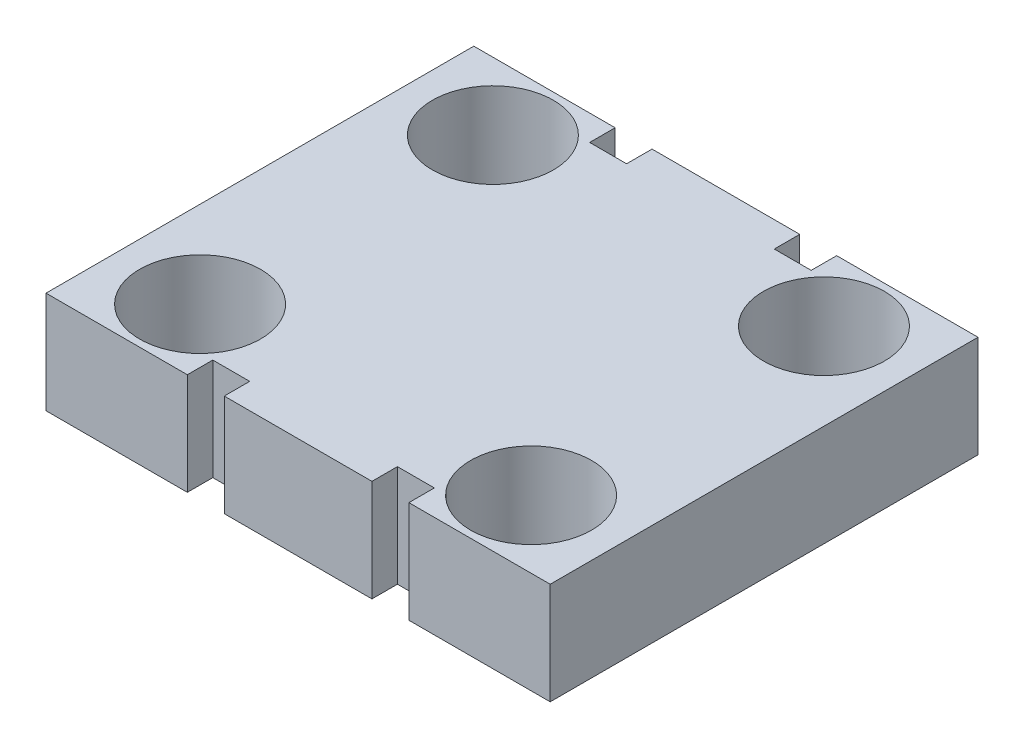
SolidWorks part; units mm, degrees
ref_plane "Płaszczyzna przednia" through (0, 0, 0) normal (0, 0, 1) x (1, 0, 0)
ref_plane "Płaszczyzna górna" through (0, 0, 0) normal (0, 1, 0) x (1, 0, 0)
ref_plane "Płaszczyzna prawa" through (0, 0, 0) normal (1, 0, 0) x (0, 0, -1)
sketch "Sketch1" plane through (0, 0, 0) normal (0, 1, 0) x (1, 0, 0)
  line L1 (-40, 34) -> (0, 34)
  line L2 (-40, 34) -> (-40, 0)
  line L3 (-40, 0) -> (0, 0)
  line L4 (0, 34) -> (0, 0)
  dimension "D1" = 40
  dimension "D2" = 34
extrude "Boss-Extrude1" add sketch "Sketch1" along normal blind 8
sketch "Sketch2" plane through (0, 8, 0) normal (0, 1, 0) x (1, 0, 0)
  line L0 (-40, 17) -> (-9.7076, 17) construction
  line L1 (-20, 34) -> (-20, -8.7627) construction
  line L2 (-40, 34) -> (-40, 0) construction
  line L3 (0, 34) -> (-40, 34) construction
  circle A0 centre (-33, 28.5) radius 4.75
  circle A1 centre (-33, 5.5) radius 4.75
  circle A2 centre (-7, 5.5) radius 4.75
  circle A3 centre (-7, 28.5) radius 4.75
  dimension "D1" = 9.5
  dimension "D2" = 7
  dimension "D3" = 5.5
extrude "Cut-Extrude1" cut sketch "Sketch2" against normal blind 7
sketch "Sketch3" plane through (0, 0, 0) normal (0, -1, 0) x (1, 0, 0)
  line L0 (-40, 0) -> (0, -34) construction
  circle A0 centre (-20, -17) radius 5.5
  point P3 (-20, -17)
  dimension "D1" = 11
extrude "Cut-Extrude2" cut sketch "Sketch3" against normal blind 6
sketch "Sketch4" plane through (0, 0, 0) normal (0, -1, 0) x (1, 0, 0)
  line L0 (-20, 0) -> (-20, -34) construction
  line L1 (-40, -17) -> (0, -17) construction
  line L2 (-40, 0) -> (0, 0) construction
  line L3 (0, -34) -> (-40, -34) construction
  line L4 (-40, -34) -> (-40, 0) construction
  line L5 (0, 0) -> (0, -34) construction
  line L6 (-11.5, -2) -> (-14, -2)
  line L7 (-28.5, 0) -> (-26, 0)
  line L8 (-28.5, 0) -> (-28.5, -2)
  line L9 (-28.5, -2) -> (-26, -2)
  line L10 (-26, 0) -> (-26, -2)
  line L11 (-14, 0) -> (-14, -2)
  line L12 (-11.5, 0) -> (-14, 0)
  line L13 (-11.5, 0) -> (-11.5, -2)
  line L14 (-11.5, -34) -> (-11.5, -32)
  line L15 (-11.5, -34) -> (-14, -34)
  line L16 (-14, -34) -> (-14, -32)
  line L17 (-11.5, -32) -> (-14, -32)
  line L18 (-28.5, -32) -> (-26, -32)
  line L19 (-26, -34) -> (-26, -32)
  line L20 (-28.5, -34) -> (-26, -34)
  line L21 (-28.5, -34) -> (-28.5, -32)
  dimension "D1" = 2.5
  dimension "D2" = 2
  dimension "D3" = 6
extrude "Cut-Extrude3" cut sketch "Sketch4" against normal blind 15
sketch "Sketch5" plane through (0, 0, 0) normal (0, -1, 0) x (1, 0, 0)
  line L40 (-39.8, -33.8) -> (-28.7, -33.8)
  line L41 (-28.7, -33.8) -> (-28.7, -31.8)
  line L42 (-28.7, -31.8) -> (-25.8, -31.8)
  line L43 (-25.8, -31.8) -> (-25.8, -33.8)
  line L44 (-25.8, -33.8) -> (-14.2, -33.8)
  line L45 (-14.2, -33.8) -> (-14.2, -31.8)
  line L46 (-14.2, -31.8) -> (-11.3, -31.8)
  line L47 (-11.3, -31.8) -> (-11.3, -33.8)
  line L48 (-11.3, -33.8) -> (-0.2, -33.8)
  line L49 (-0.2, -33.8) -> (-0.2, -0.2)
  line L50 (-0.2, -0.2) -> (-11.3, -0.2)
  line L51 (-11.3, -0.2) -> (-11.3, -2.2)
  line L52 (-11.3, -2.2) -> (-14.2, -2.2)
  line L53 (-14.2, -2.2) -> (-14.2, -0.2)
  line L54 (-14.2, -0.2) -> (-25.8, -0.2)
  line L55 (-25.8, -0.2) -> (-25.8, -2.2)
  line L56 (-25.8, -2.2) -> (-28.7, -2.2)
  line L57 (-28.7, -2.2) -> (-28.7, -0.2)
  line L58 (-28.7, -0.2) -> (-39.8, -0.2)
  line L59 (-39.8, -0.2) -> (-39.8, -33.8)
  line L60 (-39.8, -33.8) -> (-28.7, -33.8)
  line L61 (-28.7, -33.8) -> (-28.7, -31.8)
  line L62 (-28.7, -31.8) -> (-25.8, -31.8)
  line L63 (-25.8, -31.8) -> (-25.8, -33.8)
  line L64 (-25.8, -33.8) -> (-14.2, -33.8)
  line L65 (-14.2, -33.8) -> (-14.2, -31.8)
  line L66 (-14.2, -31.8) -> (-11.3, -31.8)
  line L67 (-11.3, -31.8) -> (-11.3, -33.8)
  line L68 (-11.3, -33.8) -> (-0.2, -33.8)
  line L69 (-0.2, -33.8) -> (-0.2, -0.2)
  line L70 (-0.2, -0.2) -> (-11.3, -0.2)
  line L71 (-11.3, -0.2) -> (-11.3, -2.2)
  line L72 (-11.3, -2.2) -> (-14.2, -2.2)
  line L73 (-14.2, -2.2) -> (-14.2, -0.2)
  line L74 (-14.2, -0.2) -> (-25.8, -0.2)
  line L75 (-25.8, -0.2) -> (-25.8, -2.2)
  line L76 (-25.8, -2.2) -> (-28.7, -2.2)
  line L77 (-28.7, -2.2) -> (-28.7, -0.2)
  line L78 (-28.7, -0.2) -> (-39.8, -0.2)
  line L79 (-39.8, -0.2) -> (-39.8, -33.8)
  line L80 (-40, -34) -> (-28.5, -34)
  line L81 (-28.5, -34) -> (-28.5, -32)
  line L82 (-28.5, -32) -> (-26, -32)
  line L83 (-26, -32) -> (-26, -34)
  line L84 (-26, -34) -> (-14, -34)
  line L85 (-14, -34) -> (-14, -32)
  line L86 (-14, -32) -> (-11.5, -32)
  line L87 (-11.5, -32) -> (-11.5, -34)
  line L88 (-11.5, -34) -> (0, -34)
  line L89 (0, -34) -> (0, 0)
  line L90 (0, 0) -> (-11.5, 0)
  line L91 (-11.5, 0) -> (-11.5, -2)
  line L92 (-11.5, -2) -> (-14, -2)
  line L93 (-14, -2) -> (-14, 0)
  line L94 (-14, 0) -> (-26, 0)
  line L95 (-26, 0) -> (-26, -2)
  line L96 (-26, -2) -> (-28.5, -2)
  line L97 (-28.5, -2) -> (-28.5, 0)
  line L98 (-28.5, 0) -> (-40, 0)
  line L99 (-40, 0) -> (-40, -34)
  line L100 (-40, -34) -> (-28.5, -34)
  line L101 (-28.5, -34) -> (-28.5, -32)
  line L102 (-28.5, -32) -> (-26, -32)
  line L103 (-26, -32) -> (-26, -34)
  line L104 (-26, -34) -> (-14, -34)
  line L105 (-14, -34) -> (-14, -32)
  line L106 (-14, -32) -> (-11.5, -32)
  line L107 (-11.5, -32) -> (-11.5, -34)
  line L108 (-11.5, -34) -> (0, -34)
  line L109 (0, -34) -> (0, 0)
  line L110 (0, 0) -> (-11.5, 0)
  line L111 (-11.5, 0) -> (-11.5, -2)
  line L112 (-11.5, -2) -> (-14, -2)
  line L113 (-14, -2) -> (-14, 0)
  line L114 (-14, 0) -> (-26, 0)
  line L115 (-26, 0) -> (-26, -2)
  line L116 (-26, -2) -> (-28.5, -2)
  line L117 (-28.5, -2) -> (-28.5, 0)
  line L118 (-28.5, 0) -> (-40, 0)
  line L119 (-40, 0) -> (-40, -34)
  dimension "D1" = 0.2
  dimension "D2" = 0
extrude "Cut-Extrude4" cut sketch "Sketch5" against normal through all
